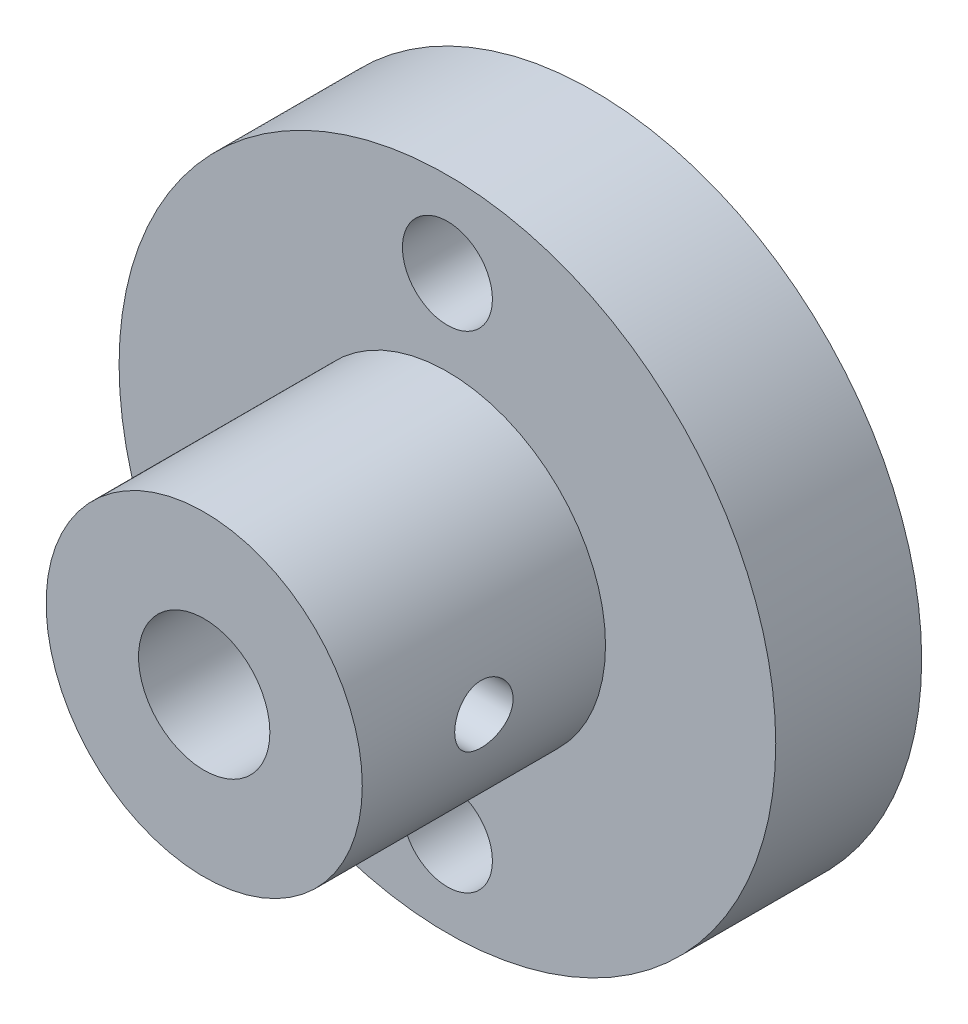
SolidWorks part; units mm, degrees
ref_plane "Front Plane" through (0, 0, 0) normal (0, 0, 1) x (1, 0, 0)
ref_plane "Top Plane" through (0, 0, 0) normal (0, 1, 0) x (1, 0, 0)
ref_plane "Right Plane" through (0, 0, 0) normal (1, 0, 0) x (0, 0, -1)
sketch "Sketch2" plane through (0, 0, 0) normal (0, 0, 1) x (1, 0, 0)
  circle A0 centre (0, 0) radius 13.5
  dimension "D1" = 27
extrude "Boss-Extrude1" add sketch "Sketch2" along normal blind 6
sketch "Sketch3" plane through (0, 0, 6) normal (0, 0, 1) x (1, 0, 0)
  circle A0 centre (0, 0) radius 6.5
  circle A1 centre (0, 0) radius 2.5
  dimension "D1" = 5
  dimension "D2" = 4
extrude "Boss-Extrude2" add sketch "Sketch3" along normal blind 10
sketch "Sketch4" plane through (0, 0, 0) normal (1, 0, 0) x (0, -1, 0)
  line L2 (-13.5, -6) -> (13.5, -6) construction
  circle A0 centre (0, -11) radius 1.2
  dimension "D1" = 2.4
  dimension "D2" = 5
extrude "Cut-Extrude1" cut sketch "Sketch4" against normal blind 25 and the other way blind 25
sketch "Sketch5" plane through (0, 0, 6) normal (0, 0, 1) x (1, 0, 0)
  circle A0 centre (0, 10) radius 1.85
  circle A1 centre (0, 0) radius 13.5 construction
  dimension "D1" = 3.7
  dimension "D2" = 10
ref_axis "Axis1" through (0, 0, -0.8) along (0, 0, 1)
sketch "Sketch6" plane through (0, 0, 6) normal (0, 0, 1) x (1, 0, 0)
  circle A0 centre (0, 0) radius 2.7
  dimension "D1" = 5.4
extrude "Cut-Extrude3" cut sketch "Sketch6" against normal blind 20 and the other way blind 50
extrude "Cut-Extrude4" cut sketch "Sketch5" against normal blind 10
mirror "Mirror1" about plane through (0, 0, 0) normal (0, 1, 0) of "Cut-Extrude4"
sketch "Sketch7" plane through (0, 0, 6) normal (0, 0, 1) x (1, 0, 0)
  circle A0 centre (0, 10) radius 3.175
  dimension "D1" = 6.35
